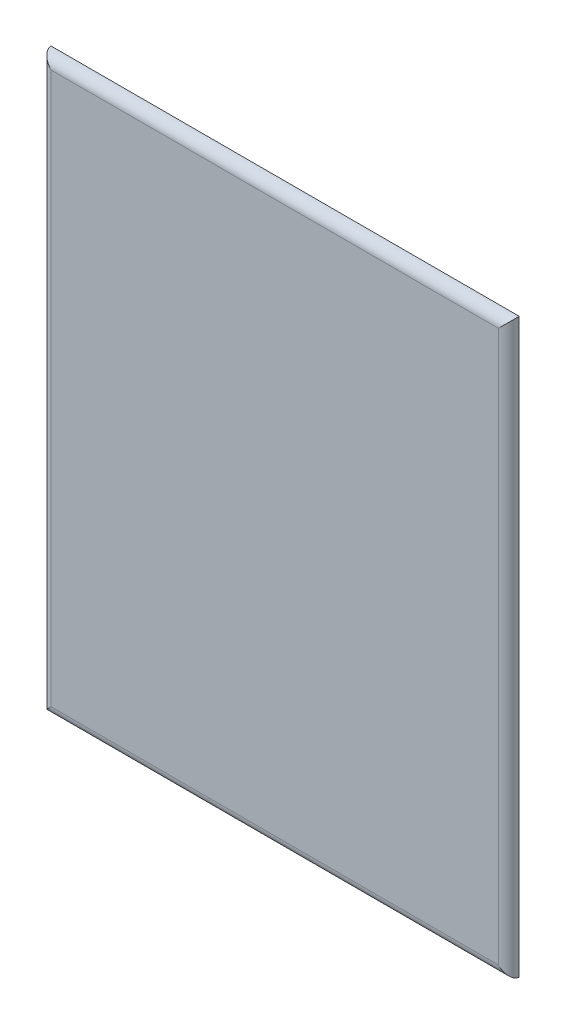
SolidWorks part; units mm, degrees
ref_plane "Plan de face" through (0, 0, 0) normal (0, 0, 1) x (1, 0, 0)
ref_plane "Plan de dessus" through (0, 0, 0) normal (0, 1, 0) x (1, 0, 0)
ref_plane "Plan de droite" through (0, 0, 0) normal (1, 0, 0) x (0, 0, -1)
sketch "Esquisse1" plane through (0, 0, 0) normal (0, 0, 1) x (1, 0, 0)
  line L1 (-67.5, -82.5) -> (67.5, -82.5)
  line L2 (-67.5, -82.5) -> (-67.5, 82.5)
  line L3 (-67.5, 82.5) -> (67.5, 82.5)
  line L4 (67.5, -82.5) -> (67.5, 82.5)
  line L5 (-67.5, -82.5) -> (67.5, 82.5) construction
  line L6 (-67.5, 82.5) -> (67.5, -82.5) construction
  point P0 (0, 0)
  dimension "D1" = 135
  dimension "D2" = 165
extrude "Boss.-Extru.1" add sketch "Esquisse1" along normal blind 3
fillet "Congé1" radius 3 4 edges at (0, -82.5, 3) (0, 82.5, 3) (67.5, 0, 3) (-67.5, 0, 3)
sketch "Esquisse2" plane through (0, 0, 0) normal (0, 0, -1) x (-1, 0, 0)
  line L0 (-67.5, 82.5) -> (67.5, -82.5) construction
  line L2 (-14.5, -16.5) -> (14.5, -16.5)
  line L3 (-16.5, -14.5) -> (-16.5, 14.5)
  line L4 (-14.5, 16.5) -> (14.5, 16.5)
  line L5 (16.5, -14.5) -> (16.5, 14.5)
  line L6 (-16.5, -16.5) -> (16.5, 16.5) construction
  line L7 (-16.5, 16.5) -> (16.5, -16.5) construction
  arc A0 (-14.5, -16.5) -> (-16.5, -14.5) centre (-14.5, -14.5) cw
  arc A1 (14.5, -16.5) -> (16.5, -14.5) centre (14.5, -14.5) ccw
  arc A2 (14.5, 16.5) -> (16.5, 14.5) centre (14.5, 14.5) cw
  arc A3 (-16.5, 14.5) -> (-14.5, 16.5) centre (-14.5, 14.5) cw
  point P4 (0, 0)
  dimension "D3" = 2
  dimension "D1" = 33
  dimension "D2" = 33
extrude "Boss.-Extru.2" add sketch "Esquisse2" along normal blind 5
fillet "Congé2" radius 2 8 edges at (-16.5, 0, -5) (-15.9142, -15.9142, -5) (0, -16.5, -5) (15.9142, -15.9142, -5) (16.5, 0, -5) (15.9142, 15.9142, -5) (0, 16.5, -5) (-15.9142, 15.9142, -5)
sketch "Esquisse3" plane through (-16.5, 0, 0) normal (-1, 0, 0) x (0, 0, 1)
  line L0 (-3, 14.5) -> (0, -14.5) construction
  circle A0 centre (-1.5, 0) radius 0.75
extrude "Boss.-Extru.3" add sketch "Esquisse3" along normal blind 5
